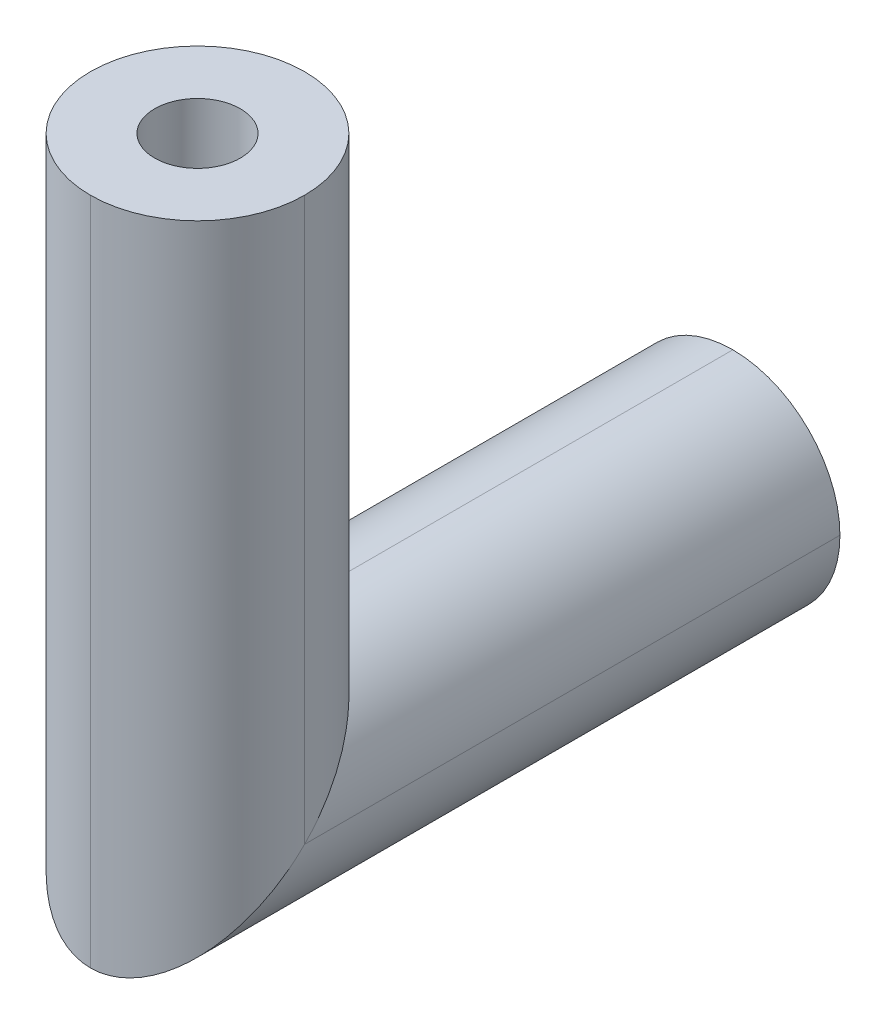
SolidWorks part; units mm, degrees
ref_plane "Plan de face" through (0, 0, 0) normal (0, 0, 1) x (1, 0, 0)
ref_plane "Plan de dessus" through (0, 0, 0) normal (0, 1, 0) x (1, 0, 0)
ref_plane "Plan de droite" through (0, 0, 0) normal (1, 0, 0) x (0, 0, -1)
sketch "Esquisse4" plane through (0, 0, 0) normal (1, 0, 0) x (0, 0, -1)
  line L0 (4, 4) -> (12, 4)
  line L1 (0, 0) -> (4, 0)
  line L2 (0, 0) -> (0, 12.5)
  line L3 (0, 12.5) -> (4, 12.5)
  line L4 (4, 0) -> (4, 12.5)
  line L5 (12, 4) -> (12, 0)
  line L6 (12, 0) -> (4, 0)
  line L7 (4, 4) -> (4, 0) construction
  dimension "D1" = 12.5
  dimension "D2" = 4
  dimension "D3" = 90
  dimension "D5" = 4
  dimension "D6" = 8
extrude "Boss.-Extru.2" add sketch "Esquisse4" along normal blind 4 contours L0 L7 L6 L5 | L7 L4 L6 | L1 L4 L3 L2 region at (0, 2, -8) region at (0, 6.25, -2)
sketch "Esquisse10" plane through (0, 12.5, 0) normal (0, 1, 0) x (1, 0, 0)
  line L0 (0, 2) -> (4, 2) construction
  line L1 (0, 0) -> (0, 4) construction
  line L2 (4, 0) -> (4, 4) construction
  circle A0 centre (2, 2) radius 0.8
  dimension "D1" = 1.6
extrude "Enlèv. mat.-Extru.3" cut sketch "Esquisse10" against normal up to surface (8.5 mm away) up to face at (2, 4, -8)
sketch "Esquisse11" plane through (0, 0, 0) normal (0, -1, 0) x (1, 0, 0)
  line L0 (0, 0) -> (4, -4) construction
  line L1 (4, -12) -> (4, 0) construction
  line L2 (4, 0) -> (4, -4) construction
  line L3 (4, 0) -> (0, 0) construction
  circle A0 centre (2, -2) radius 0.8
  dimension "D1" = 1.6
extrude "Enlèv. mat.-Extru.4" cut sketch "Esquisse11" against normal blind 2
sketch "Esquisse6" plane through (0, 12.5, 0) normal (0, 1, 0) x (1, 0, 0)
  line L0 (0, 2) -> (4, 2) construction
  line L1 (0, 0) -> (0, 4) construction
  line L2 (4, 0) -> (4, 4) construction
  circle A0 centre (2, 2) radius 0.8
  dimension "D1" = 1.6
sketch "Esquisse7" plane through (0, 0, -12) normal (0, 0, -1) x (1, 0, 0)
  line L0 (0, -2) -> (4, -2) construction
  line L1 (0, -4) -> (0, 0) construction
  line L2 (4, -4) -> (4, 0) construction
  circle A0 centre (2, -2) radius 0.8
  dimension "D1" = 1.6
extrude "Enlèv. mat.-Extru.2" cut sketch "Esquisse7" against normal blind 8
fillet "Congé4" radius 2 8 edges at (4, 0, -6) (0, 0, -6) (4, 8.25, -4) (0, 8.25, -4) (4, 4, -8) (0, 4, -8) (4, 6.25, 0) (0, 6.25, 0)
